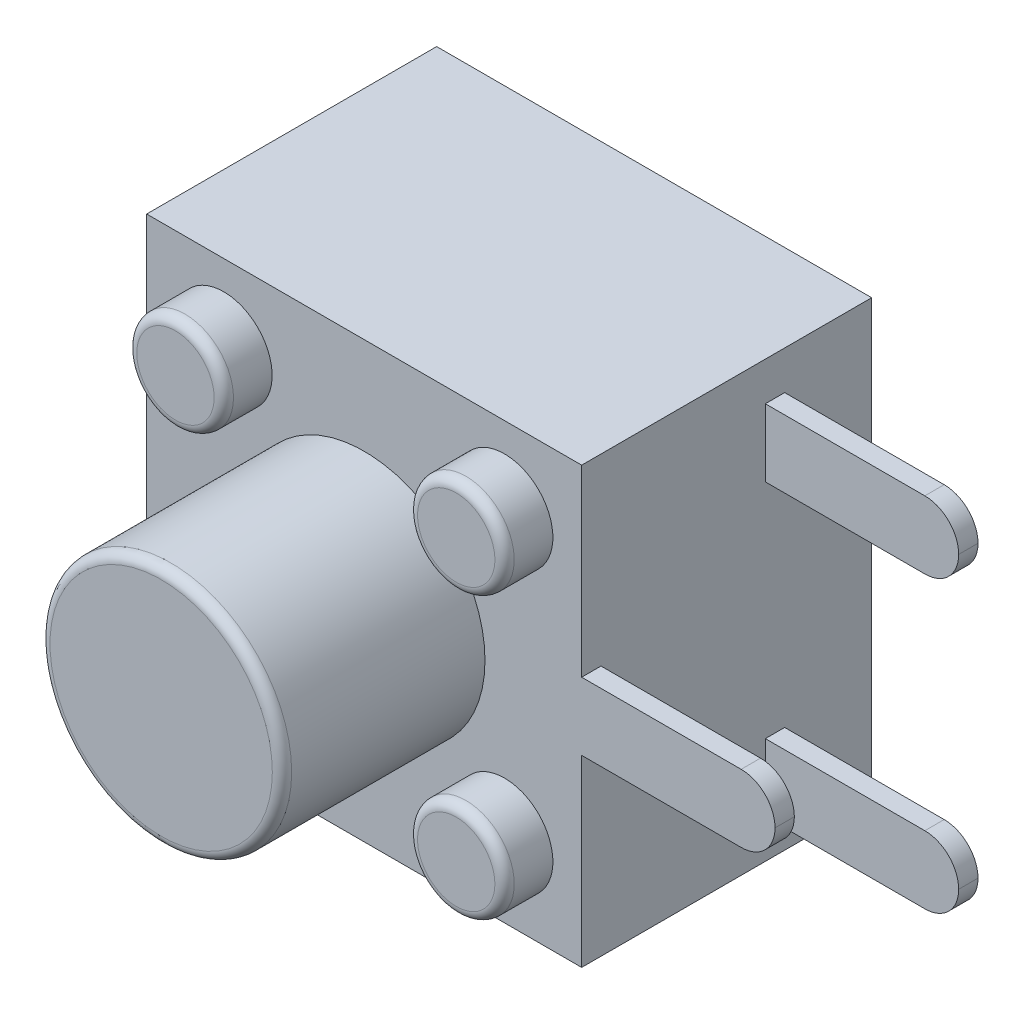
SolidWorks part; units mm, degrees
ref_plane "Front" through (0, 0, 0) normal (0, 0, 1) x (1, 0, 0)
ref_plane "Top" through (0, 0, 0) normal (0, 1, 0) x (1, 0, 0)
ref_plane "Right" through (0, 0, 0) normal (1, 0, 0) x (0, 0, -1)
sketch "Sketch1" plane through (0, 0, 0) normal (0, 0, 1) x (1, 0, 0)
  line L1 (-2.25, -2.25) -> (2.25, -2.25)
  line L2 (-2.25, -2.25) -> (-2.25, 2.25)
  line L3 (-2.25, 2.25) -> (2.25, 2.25)
  line L4 (2.25, -2.25) -> (2.25, 2.25)
  line L5 (-2.25, -2.25) -> (2.25, 2.25) construction
  line L6 (-2.25, 2.25) -> (2.25, -2.25) construction
  point P0 (0, 0)
  dimension "D1" = 4.5
  dimension "D2" = 4.5
extrude "Boss-Extrude1" add sketch "Sketch1" along normal blind 3
sketch "Sketch4" plane through (0, 0, 3) normal (0, 0, 1) x (1, 0, 0)
  line L0 (-2.25, 0) -> (2.25, 0) construction
  line L1 (-2.25, 2.25) -> (-2.25, -2.25) construction
  line L2 (2.25, -2.25) -> (2.25, 2.25) construction
  line L3 (0, 0) -> (-2.25, 2.25) construction
  line L4 (2.25, 2.25) -> (-2.25, 2.25) construction
  line L5 (0, 2.25) -> (0, -2.25) construction
  line L6 (-2.25, -2.25) -> (2.25, -2.25) construction
  line L7 (0, -2.25) -> (0, 2.25) construction
  circle A0 centre (-1.4522, 1.4522) radius 0.5
  circle A1 centre (1.4522, 1.4522) radius 0.5
  circle A2 centre (1.4522, -1.4522) radius 0.5
  circle A3 centre (-1.4522, -1.4522) radius 0.5
  point P17 (0, 0)
  dimension "D1" = 1
extrude "Boss-Extrude3" add sketch "Sketch4" along normal blind 0.5
fillet "Fillet1" radius 0.1 4 edges at (0.9522, 1.4522, 3.5) (1.9522, -1.4522, 3.5) (-1.9522, -1.4522, 3.5) (-0.9522, 1.4522, 3.5)
sketch "Sketch5" plane through (0, 0, 3) normal (0, 0, 1) x (1, 0, 0)
  circle A0 centre (0, 0) radius 1.25
  dimension "D1" = 2.5
extrude "Boss-Extrude4" add sketch "Sketch5" along normal blind 2.1
fillet "Fillet2" radius 0.1 1 edges at (1.25, 0, 5.1)
sketch "Sketch6" plane through (0, 0, 3) normal (0, 0, 1) x (1, 0, 0)
  line L0 (0, 0) -> (3.25, 0) construction
  line L1 (2.25, -2.25) -> (2.25, 2.25) construction
  line L2 (4.25, -0.35) -> (2.25, -0.35)
  line L3 (4.25, -0.35) -> (4.25, 0.35)
  line L4 (4.25, 0.35) -> (2.25, 0.35)
  line L5 (2.25, -0.35) -> (2.25, 0.35)
  line L6 (4.25, -0.35) -> (2.25, 0.35) construction
  line L7 (4.25, 0.35) -> (2.25, -0.35) construction
  dimension "D1" = 0.7
  dimension "D2" = 2
extrude "Boss-Extrude5" add sketch "Sketch6" against normal blind 0.2
ref_plane "Plane1" through (0, 0, 1) normal (0, 0, -1) x (-1, 0, 0)
sketch "Sketch7" plane through (0, 0, 1) normal (0, 0, -1) x (-1, 0, 0)
  line L0 (-2.25, -2.25) -> (-2.25, -0.35) construction
  line L1 (-2.25, -1.85) -> (-4.25, -1.85)
  line L2 (-2.25, -1.85) -> (-2.25, -1.15)
  line L3 (-2.25, -1.15) -> (-4.25, -1.15)
  line L4 (-4.25, -1.85) -> (-4.25, -1.15)
  line L5 (-4.25, -0.35) -> (-4.25, 0.35) construction
  line L6 (-4.25, -0.35) -> (-4.25, 0.35) construction
  line L7 (0, 0) -> (-4.6858, 0) construction
  line L9 (-2.25, 1.15) -> (-4.25, 1.15)
  line L10 (-2.25, 1.85) -> (-2.25, 1.15)
  line L11 (-4.25, 1.85) -> (-4.25, 1.15)
  line L12 (-2.25, 1.85) -> (-4.25, 1.85)
  point P10 (-4.25, 0)
  point P11 (-4.25, -1.5)
  dimension "D1" = 2
  dimension "D2" = 1.5
extrude "Boss-Extrude6" add sketch "Sketch7" along normal mid plane 0.2
fillet "Fillet3" radius 0.35 6 edges at (4.25, 1.85, 1) (4.25, 1.15, 1) (4.25, -0.35, 2.9) (4.25, 0.35, 2.9) (4.25, -1.15, 1) (4.25, -1.85, 1)
